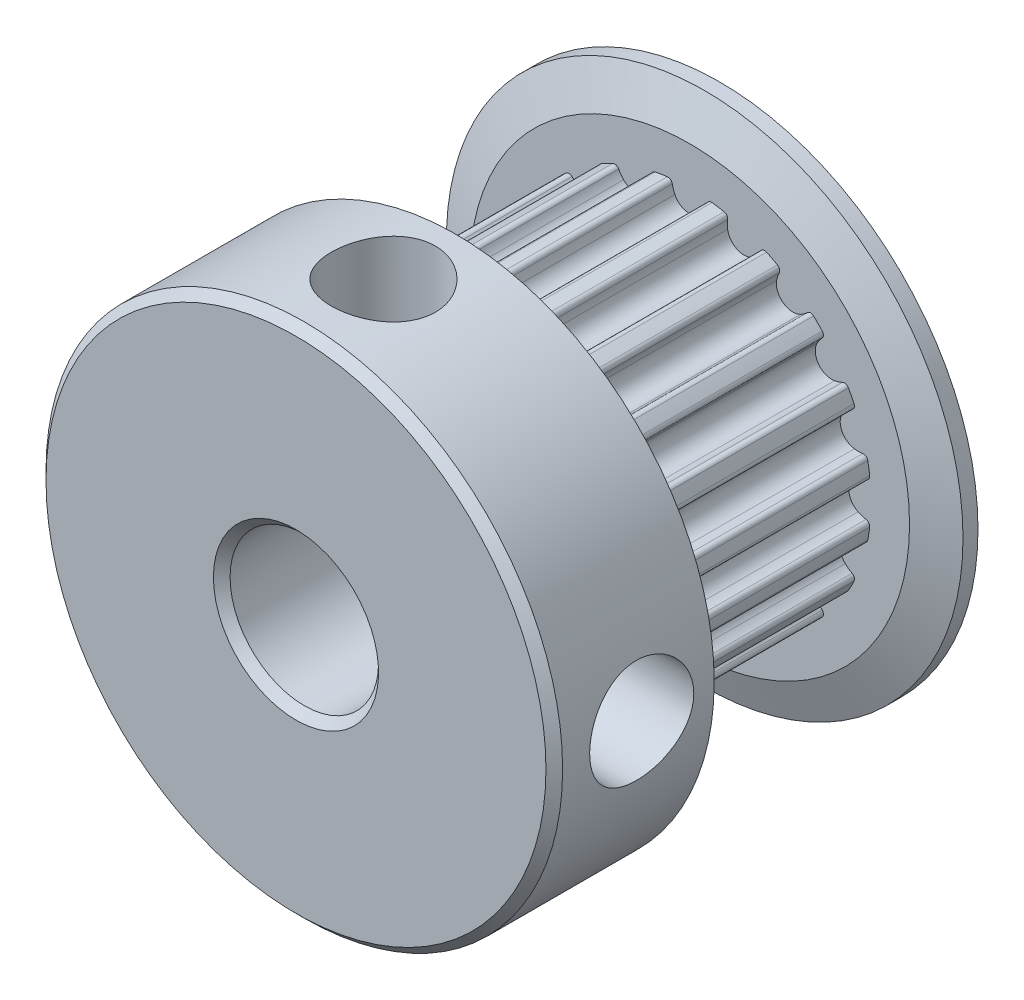
SolidWorks part; units mm, degrees
ref_plane "Front Plane" through (0, 0, 0) normal (0, 0, 1) x (1, 0, 0)
ref_plane "Top Plane" through (0, 0, 0) normal (0, 1, 0) x (1, 0, 0)
ref_plane "Right Plane" through (0, 0, 0) normal (1, 0, 0) x (0, 0, -1)
sketch "Sketch1" plane through (0, 0, 0) normal (0, 0, 1) x (1, 0, 0)
  line L1 (-1.7499, 5.3585) -> (1.7499, 5.3585) construction
  line L4 (0, 0) -> (0, 5.3585) construction
  line L5 (0, 5.3585) -> (0, 11.2111) construction
  line L6 (0, 6.3625) -> (1.9751, 6.0482) construction
  line L7 (1.9751, 6.0482) -> (2.6648, 5.8229) construction
  line L8 (1.9751, 6.0482) -> (1.7499, 5.3585) construction
  line L9 (-1.9751, 6.0482) -> (-1.7499, 5.3585) construction
  line L10 (-1.8963, 5.8067) -> (-2.841, 8.6995)
  line L11 (-2.841, 8.6995) -> (2.841, 8.6995)
  line L12 (2.841, 8.6995) -> (1.8963, 5.8067)
  circle A0 centre (0, 0) radius 6.3625 construction
  circle A1 centre (0, 0) radius 8.6995 construction
  circle A2 centre (0, 0) radius 6.1085 construction
  arc A3 (-0.4989, 5.6703) -> (0.4989, 5.6703) centre (0, 5.9135) ccw
  arc A4 (-0.4989, 5.6703) -> (-0.5855, 5.9387) centre (0.4, 6.1085) cw
  arc A5 (-1.8963, 5.8067) -> (-0.7518, 6.0621) centre (0, 0) cw
  arc A6 (-0.5855, 5.9387) -> (-0.7518, 6.0621) centre (-0.7333, 5.9132) ccw
  arc A7 (1.8963, 5.8067) -> (0.7518, 6.0621) centre (0, 0) ccw
  arc A8 (0.5855, 5.9387) -> (0.7518, 6.0621) centre (0.7333, 5.9132) cw
  arc A9 (0.4989, 5.6703) -> (0.5855, 5.9387) centre (-0.4, 6.1085) ccw
  point P6 (0, 20.9083)
  point P11 (0, 6.3625)
  point P13 (0, 8.6995)
  point P14 (0, 6.1085)
  dimension "D1" = 9.6972
  dimension "D2" = 4.8486
sketch "Sketch2" plane through (0, 0, 0) normal (1, 0, 0) x (0, 0, -1)
  line L0 (-7.135, 2.5) -> (7.135, 2.5)
  line L1 (-7.135, 2.5) -> (-7.135, 8.6995)
  line L2 (-1.75, 8.6995) -> (-7.135, 8.6995)
  line L3 (-2.255, 2.5) -> (-2.255, 8.6995) construction
  line L4 (-2.255, 8.6995) -> (-1.245, 8.6995) construction
  line L5 (-1.245, 8.6995) -> (-1.245, 6.1085) construction
  line L6 (-1.245, 6.1085) -> (6.125, 6.1085)
  line L7 (6.125, 6.1085) -> (6.125, 8.6995) construction
  line L8 (6.125, 8.6995) -> (7.135, 8.6995) construction
  line L9 (7.135, 8.6995) -> (7.135, 2.5)
  line L10 (-7.135, 0) -> (7.135, 0) construction
  line L11 (6.63, 8.6995) -> (6.125, 7.404)
  line L12 (-1.245, 7.404) -> (-1.75, 8.6995)
  line L14 (-1.245, 7.404) -> (-1.245, 6.1085)
  line L15 (6.125, 6.1085) -> (6.125, 7.404)
  line L16 (6.63, 8.6995) -> (7.135, 8.6995)
  arc A0 (-1.245, 7.404) -> (-1.75, 8.6995) centre (-3.1592, 7.404) ccw construction
  arc A1 (6.125, 7.404) -> (6.63, 8.6995) centre (8.0392, 7.404) cw construction
  point P12 (-1.245, 7.404)
  point P14 (-1.75, 8.6995)
  point P20 (6.125, 7.404)
  point P21 (6.63, 8.6995)
  point P25 (6.125, 0)
  point P26 (-1.245, 0)
  dimension "OA" = 14.27
  dimension "Bore" = 5
  dimension "Outside Width" = 8.38
  dimension "Inside Width" = 7.37
revolve "Revolve1" add sketch "Sketch2" angle 360 mid plane about L10
sketch "Sketch3" plane through (0, 0, 0) normal (0, 0, 1) x (1, 0, 0)
  line L6 (2.841, 8.6995) -> (-2.841, 8.6995)
  line L7 (1.8963, 5.8067) -> (2.841, 8.6995)
  line L8 (-2.841, 8.6995) -> (-1.8963, 5.8067)
  line L9 (2.841, 8.6995) -> (-2.841, 8.6995)
  line L10 (1.8963, 5.8067) -> (2.841, 8.6995)
  line L11 (-2.841, 8.6995) -> (-1.8963, 5.8067)
  arc A8 (1.8963, 5.8067) -> (0.7518, 6.0621) centre (0, 0) ccw
  arc A9 (0.7518, 6.0621) -> (0.5855, 5.9387) centre (0.7333, 5.9132) ccw
  arc A10 (0.4989, 5.6703) -> (0.5855, 5.9387) centre (-0.4, 6.1085) ccw
  arc A11 (-0.4989, 5.6703) -> (0.4989, 5.6703) centre (0, 5.9135) ccw
  arc A12 (-0.5855, 5.9387) -> (-0.4989, 5.6703) centre (0.4, 6.1085) ccw
  arc A13 (-0.5855, 5.9387) -> (-0.7518, 6.0621) centre (-0.7333, 5.9132) ccw
  arc A14 (-0.7518, 6.0621) -> (-1.8963, 5.8067) centre (0, 0) ccw
  arc A15 (1.8963, 5.8067) -> (0.7518, 6.0621) centre (0, 0) ccw
  arc A16 (0.7518, 6.0621) -> (0.5855, 5.9387) centre (0.7333, 5.9132) ccw
  arc A17 (0.4989, 5.6703) -> (0.5855, 5.9387) centre (-0.4, 6.1085) ccw
  arc A18 (-0.4989, 5.6703) -> (0.4989, 5.6703) centre (0, 5.9135) ccw
  arc A19 (-0.5855, 5.9387) -> (-0.4989, 5.6703) centre (0.4, 6.1085) ccw
  arc A20 (-0.5855, 5.9387) -> (-0.7518, 6.0621) centre (-0.7333, 5.9132) ccw
  arc A21 (-0.7518, 6.0621) -> (-1.8963, 5.8067) centre (0, 0) ccw
  dimension "D1" = 0
extrude "Cut-Extrude1" cut sketch "Sketch3" against normal up to vertex (6.125 mm away) from vertex up to point (0, 6.1085, -6.125) starting at point (0, 6.1085, 1.245)
pattern_circular "CirPattern1" count 20 over 360 about axis through (0, 0, 7.135) along (0, 0, 1) of "Cut-Extrude1"
sketch "Sketch4" plane through (0, 0, 0) normal (1, 0, 0) x (0, -1, 0)
  line L0 (0, -1.245) -> (0, -7.135) construction
  line L1 (-2.5, -7.135) -> (2.5, -7.135) construction
  line L2 (7.404, -1.245) -> (-7.404, -1.245) construction
  circle A0 centre (0, -4.19) radius 1.7526
extrude "Cut-Extrude2" cut sketch "Sketch4" along normal through all
ref_plane "Plane1" through (0, 0, 4.19) normal (0, 0, 1) x (1, 0, 0)
sketch "Sketch5" plane through (0, 0, 4.19) normal (0, 0, 1) x (1, 0, 0)
  line L0 (0, 0) -> (0, 8.6995) construction
  line L1 (2.5, -1.3716) -> (2.5, 0)
  line L2 (2.881, -1.7526) -> (8.1401, -1.7526)
  line L3 (2.5, 0) -> (8.6995, 0) construction
  line L4 (2.5, 0) -> (8.5211, 0)
  line L5 (8.5211, 0) -> (8.5211, -1.3716)
  line L6 (2.881, -1.7526) -> (2.5, -1.3716)
  line L7 (8.5211, -1.3716) -> (8.1401, -1.7526)
  circle A0 centre (0, 0) radius 8.6995 construction
  circle A1 centre (0, 0) radius 2.5 construction
  point P2 (2.5, -1.7526)
  point P11 (8.5211, -1.7526)
revolve "Revolve2" [suppressed] add sketch "Sketch5" angle 360 mid plane about L4
sketch "Sketch6" [suppressed] plane through (8.5211, 5.3841, 0) normal (-1, 0, 0) x (0, -1, 0)
  line L1 (5.3841, 5.2019) -> (4.5078, 4.6959)
  line L2 (4.5078, 4.6959) -> (4.5078, 3.6841)
  line L3 (4.5078, 3.6841) -> (5.3841, 3.1781)
  line L4 (5.3841, 3.1781) -> (6.2604, 3.6841)
  line L5 (6.2604, 3.6841) -> (6.2604, 4.6959)
  line L6 (6.2604, 4.6959) -> (5.3841, 5.2019)
  circle A0 centre (5.3841, 4.19) radius 0.8763 construction
  dimension "D1" = 1.7526
extrude "Cut-Extrude3" [suppressed] cut sketch "Sketch6" along normal blind 1.3144
pattern_circular "CirPattern3" count 2 every 90 about axis through (0, 0, 7.135) along (0, 0, 1) of "Cut-Extrude2", "Revolve2", "Cut-Extrude3"
chamfer "Chamfer1" distance 0.2807 angle 45 2 edges at (2.5, 0, 7.135) (8.6995, 0, 7.135)
ref_axis "Center Axis 1" through (0, 0, -7.135) along (0, 0, 1)
ref_plane "Contact Plane 1" through (0, 0, 7.135) normal (0, 0, 1) x (1, 0, 0)
ref_plane "Contact Plane 2" through (0, 0, -7.135) normal (0, 0, -1) x (-1, 0, 0)
equation "\"D2@Sketch1\"= \"D1@Sketch1\" / 2"
equation "\"D1@Sketch6\" = \"Set Screw@Sketch4\" / 2"
equation "\"D1@Cut-Extrude3\" = \"D1@Sketch6\"*.75"
